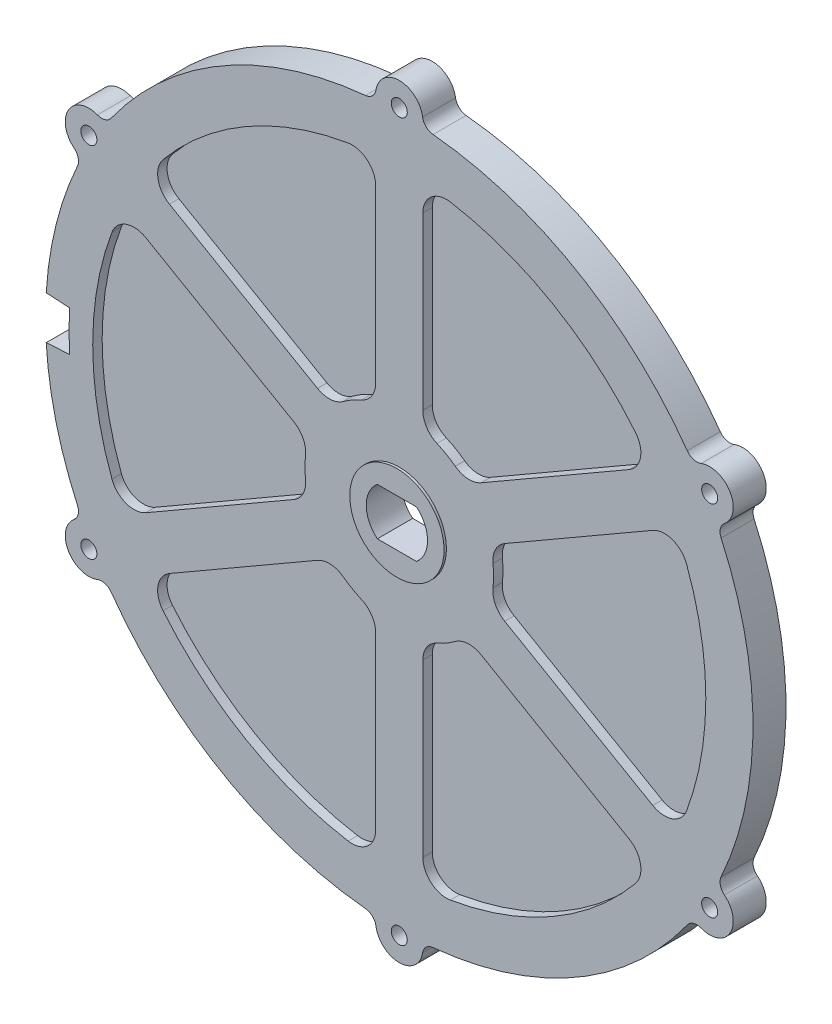
SolidWorks part; units mm, degrees
material "PETG"
ref_plane "Front Plane" through (0, 0, 0) normal (0, 0, 1) x (1, 0, 0)
ref_plane "Top Plane" through (0, 0, 0) normal (0, 1, 0) x (1, 0, 0)
ref_plane "Right Plane" through (0, 0, 0) normal (1, 0, 0) x (0, 0, -1)
sketch "Sketch2" plane through (0, 0, 0) normal (0, 0, 1) x (1, 0, 0)
  line L0 (4.1533, 5) -> (-4.1533, 5)
  line L1 (4.1533, -5) -> (-4.1533, -5)
  circle A0 centre (0, 0) radius 75
  circle A1 centre (0, 0) radius 6.5
  dimension "D1" = 150
  dimension "D2" = 13
  dimension "D3" = 10
extrude "Boss-Extrude1" add sketch "Sketch2" along normal mid plane 7 contours A0 A1 | L0 A1 | L1 A1 region at (0, 5.6064, 0) region at (0, -5.6064, 0) region at (-72.8787, 0, 0)
sketch "Sketch3" plane through (0, 0, 3.5) normal (0, 0, 1) x (1, 0, 0)
  circle A0 centre (0, 0) radius 10
  arc M2 (4.1533, 5) -> (4.1533, -5) centre (0, 0) cw
  line M3 (4.1533, -5) -> (-4.1533, -5)
  arc M4 (-4.1533, -5) -> (-4.1533, 5) centre (0, 0) cw
  line M5 (-4.1533, 5) -> (4.1533, 5)
  dimension "D1" = 20
extrude "Boss-Extrude2" add sketch "Sketch3" along normal blind 0.5 contours A0 M5 M2 M3 M4 region at (-9.7172, 0, 3.5)
sketch "Sketch4" plane through (0, 0, -3.5) normal (0, 0, 1) x (1, 0, 0)
  line L0 (5, 76) -> (5, 74.8331)
  line L1 (-5, 76) -> (-5, 74.8331)
  arc A0 (5, 76) -> (-5, 76) centre (0, 76) ccw
  circle A1 centre (0, 0) radius 75 construction
  circle A3 centre (0, 0) radius 75
  arc A4 (-5, 74.8331) -> (5, 74.8331) centre (0, 0) ccw
  circle M9 centre (0, 0) radius 75
  dimension "D1" = 5
  dimension "D2" = 76
  dimension "D3" = 0
extrude "Boss-Extrude3" add sketch "Sketch4" along normal up to surface (7 mm away) contours A0 L0 L1 M9 region at (0, 77.5604, -3.5) up to face at (10, 0, 3.5)
fillet "Fillet1" radius 2.5 2 edges at (-5, 74.8331, 0) (5, 74.8331, 0)
sketch "Sketch6" plane through (0, 0, -3.5) normal (0, 0, -1) x (-1, 0, 0)
  circle A0 centre (0, 76) radius 1.7
  arc A4 (4.9414, 76.7632) -> (-4.9414, 76.7632) centre (0, 76) ccw construction
  dimension "D1" = 3.4
extrude "Cut-Extrude1" cut sketch "Sketch6" against normal through all
pattern_circular "CirPattern1" count 6 over 360 about axis through (0, 0, -3.5) along (0, 0, 1) of "Boss-Extrude3", "Cut-Extrude1", "Fillet1"
sketch "Sketch7" plane through (0, 0, -3.5) normal (0, 0, -1) x (-1, 0, 0)
  line L0 (-5, 59.1608) -> (-5, 22.9129)
  line L1 (5, 59.1608) -> (5, 22.9129)
  line L2 (-5, 19.3649) -> (5, 19.3649) construction
  line L3 (48.7348, 33.9105) -> (17.3431, 15.7866)
  line L4 (53.7348, 25.2503) -> (22.3431, 7.1263)
  line L6 (53.7348, -25.2503) -> (22.3431, -7.1263)
  line L7 (48.7348, -33.9105) -> (17.3431, -15.7866)
  line L9 (5, -59.1608) -> (5, -22.9129)
  line L10 (-5, -59.1608) -> (-5, -22.9129)
  line L12 (-48.7348, -33.9105) -> (-17.3431, -15.7866)
  line L13 (-53.7348, -25.2503) -> (-22.3431, -7.1263)
  line L15 (-53.7348, 25.2503) -> (-22.3431, 7.1263)
  line L16 (-48.7348, 33.9105) -> (-17.3431, 15.7866)
  line L18 (0, 0) -> (8, 18.3303) construction
  line L19 (14.2705, 14.0126) -> (19.2705, 5.3523) construction
  line L20 (19.2705, -5.3523) -> (14.2705, -14.0126) construction
  line L21 (5, -19.3649) -> (-5, -19.3649) construction
  line L22 (-14.2705, -14.0126) -> (-19.2705, -5.3523) construction
  line L23 (-19.2705, 5.3523) -> (-14.2705, 14.0126) construction
  arc A0 (-8, 18.3303) -> (-11.8745, 16.0934) centre (0, 0) ccw
  arc A1 (-10.8333, 64.0909) -> (-50.0876, 41.4274) centre (0, 0) ccw
  arc A2 (5, 22.9129) -> (8, 18.3303) centre (10, 22.9129) ccw
  arc A3 (5, 59.1608) -> (10.8333, 64.0909) centre (10, 59.1608) cw
  arc A4 (-5, 59.1608) -> (-10.8333, 64.0909) centre (-10, 59.1608) ccw
  arc A5 (-5, 22.9129) -> (-8, 18.3303) centre (-10, 22.9129) cw
  arc A6 (22.3431, 7.1263) -> (19.8745, 2.2369) centre (24.8431, 2.7962) ccw
  arc A7 (53.7348, 25.2503) -> (60.921, 22.6635) centre (56.2348, 20.9201) cw
  arc A8 (48.7348, 33.9105) -> (50.0876, 41.4274) centre (46.2348, 38.2407) ccw
  arc A9 (17.3431, 15.7866) -> (11.8745, 16.0934) centre (14.8431, 20.1167) cw
  arc A10 (17.3431, -15.7866) -> (11.8745, -16.0934) centre (14.8431, -20.1167) ccw
  arc A11 (48.7348, -33.9105) -> (50.0876, -41.4274) centre (46.2348, -38.2407) cw
  arc A12 (53.7348, -25.2503) -> (60.921, -22.6635) centre (56.2348, -20.9201) ccw
  arc A13 (22.3431, -7.1263) -> (19.8745, -2.2369) centre (24.8431, -2.7962) cw
  arc A14 (-5, -22.9129) -> (-8, -18.3303) centre (-10, -22.9129) ccw
  arc A15 (-5, -59.1608) -> (-10.8333, -64.0909) centre (-10, -59.1608) cw
  arc A16 (5, -59.1608) -> (10.8333, -64.0909) centre (10, -59.1608) ccw
  arc A17 (5, -22.9129) -> (8, -18.3303) centre (10, -22.9129) cw
  arc A18 (-22.3431, -7.1263) -> (-19.8745, -2.2369) centre (-24.8431, -2.7962) ccw
  arc A19 (-53.7348, -25.2503) -> (-60.921, -22.6635) centre (-56.2348, -20.9201) cw
  arc A20 (-48.7348, -33.9105) -> (-50.0876, -41.4274) centre (-46.2348, -38.2407) ccw
  arc A21 (-17.3431, -15.7866) -> (-11.8745, -16.0934) centre (-14.8431, -20.1167) cw
  arc A22 (-17.3431, 15.7866) -> (-11.8745, 16.0934) centre (-14.8431, 20.1167) ccw
  arc A23 (-48.7348, 33.9105) -> (-50.0876, 41.4274) centre (-46.2348, 38.2407) cw
  arc A24 (-53.7348, 25.2503) -> (-60.921, 22.6635) centre (-56.2348, 20.9201) ccw
  arc A25 (-22.3431, 7.1263) -> (-19.8745, 2.2369) centre (-24.8431, 2.7962) cw
  arc A26 (11.8745, 16.0934) -> (8, 18.3303) centre (0, 0) ccw
  arc A27 (19.8745, -2.2369) -> (19.8745, 2.2369) centre (0, 0) ccw
  arc A28 (8, -18.3303) -> (11.8745, -16.0934) centre (0, 0) ccw
  arc A29 (-11.8745, -16.0934) -> (-8, -18.3303) centre (0, 0) ccw
  arc A30 (-19.8745, 2.2369) -> (-19.8745, -2.2369) centre (0, 0) ccw
  arc A31 (50.0876, 41.4274) -> (10.8333, 64.0909) centre (0, 0) ccw
  arc A32 (60.921, -22.6635) -> (60.921, 22.6635) centre (0, 0) ccw
  arc A33 (10.8333, -64.0909) -> (50.0876, -41.4274) centre (0, 0) ccw
  arc A34 (-50.0876, -41.4274) -> (-10.8333, -64.0909) centre (0, 0) ccw
  arc A35 (-60.921, 22.6635) -> (-60.921, -22.6635) centre (0, 0) ccw
  point P8 (0, 19.3649)
  dimension "D1" = 130
  dimension "D2" = 40
  dimension "D4" = 5
  dimension "D3" = 10
  dimension "D5" = 6
extrude "Cut-Extrude2" cut sketch "Sketch7" against normal blind 2
mirror "Mirror1" about plane through (0, 0, 0) normal (0, 0, 1) of "Cut-Extrude2"
sketch "Sketch9" plane through (0, 0, 0) normal (0, 1, 0) x (1, 0, 0)
  line L0 (-7.173, 3.5) -> (-61.0677, 3.5) construction
  line L1 (-75, -3.5) -> (-70, -3.5)
  line L2 (-75, -3.5) -> (-75, 3.5)
  line L3 (-75, 3.5) -> (-70, 3.5)
  line L4 (-70, -3.5) -> (-70, 3.5)
  line L5 (-61.0677, -3.5) -> (-7.173, -3.5) construction
  line L6 (0, 0) -> (0, 49.8627) construction
  line L7 (-68.2407, 3.5) -> (-75, 3.5) construction
  line L8 (-75, 3.5) -> (-75, -3.5) construction
  dimension "D1" = 5
revolve "Cut-Revolve1" cut sketch "Sketch9" angle 7 mid plane about L6
